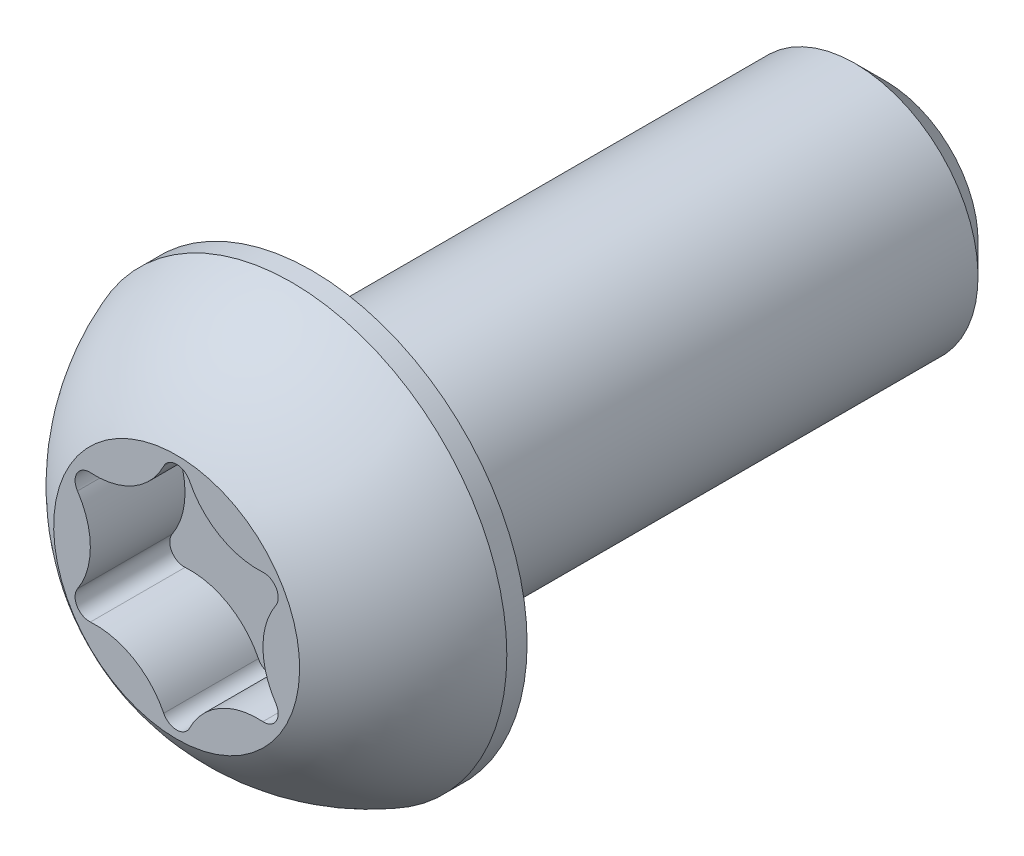
SolidWorks part; units mm, degrees
material "Plain Carbon Steel"
ref_plane "Front" through (0, 0, 0) normal (0, 0, 1) x (1, 0, 0)
ref_plane "Top" through (0, 0, 0) normal (0, 1, 0) x (1, 0, 0)
ref_plane "Right" through (0, 0, 0) normal (1, 0, 0) x (0, 0, -1)
sketch "Sketch1" plane through (0, 0, 0) normal (1, 0, 0) x (0, 0, -1)
  line L2 (-7, 3) -> (7, 3)
  line L3 (7, 3) -> (7, 0)
  line L4 (7, 0) -> (-7, 0)
  line L6 (-7.495, 5.25) -> (-7, 5.25) construction
  line L7 (7, 3) -> (7, -3) construction
  line L8 (-10.3, 0) -> (-7, 0) construction
  line L9 (-7, 5.25) -> (-7, -5.25) construction
  line L11 (-7, 3) -> (-7, 0)
  line L14 (-10.3, 0) -> (-10.3, 3) construction
  line L15 (7, -3) -> (6, -3) construction
  arc A3 (-10.3, 3) -> (-7.495, 5.25) centre (-5.5887, 0) cw construction
  point P10 (5.5, -3)
  point P15 (0, 0)
  dimension "Thread OD" = 6
  dimension "D1" = 0.495
  dimension "Head Height" = 3.3
  dimension "Head Diameter" = 10.5
  dimension "Length" = 14
  dimension "Thread Pitch" = 1
  dimension "D2" = 1.5
sketch "Sketch2" plane through (0, 0, 0) normal (0, 0, 1) x (1, 0, 0)
  line L0 (0, 0) -> (-2.4307, 1.4034)
  line L1 (0, 0) -> (-2.4307, -1.4034)
  line L2 (0, 2.8067) -> (0, 2.4559) construction
  line L3 (0, 2.4559) -> (0, 2.105) construction
  circle A0 centre (0, 0) radius 2.8067 construction
  circle A1 centre (0, 0) radius 2.105 construction
  circle A2 centre (0, 0) radius 2.4559 construction
  arc A4 (-2.4185, 1.0329) -> (-2.4185, -1.0329) centre (-3.9636, 0) cw
  arc A5 (-2.4185, 1.0329) -> (-2.4307, 1.4034) centre (-2.1268, 1.2279) cw
  arc A6 (-2.4185, -1.0329) -> (-2.4307, -1.4034) centre (-2.1268, -1.2279) ccw
  point P3 (0, -2.8067)
  dimension "Torx OD" = 5.6134
  dimension "D1" = 4.2101
  dimension "D2" = 60
sketch "Sketch12" plane through (0, 0, 0) normal (1, 0, 0) x (0, 0, -1)
  line L0 (-7, 3) -> (-7, 0) construction
  line L1 (7, 0) -> (-7, 0) construction
  line L2 (7, 3) -> (7, 0) construction
  line L3 (-7, 3) -> (7, 3) construction
  line L4 (-7, 3) -> (-7, 0)
  line L5 (7, 0) -> (-7, 0)
  line L6 (7, 3) -> (7, 0)
  line L7 (-7, 3) -> (7, 3)
revolve "Revolve1" add sketch "Sketch12" angle 360 about L5
sketch "Sketch7" plane through (0, 0, 0) normal (1, 0, 0) x (0, 0, -1)
  line L0 (-10.3, 0) -> (-10.3, 3) construction
  line L6 (-7.495, 5.25) -> (-7, 5.25) construction
  line L8 (-10.3, 0) -> (-7, 0) construction
  line L11 (-7, 5.25) -> (-7, -5.25) construction
  line L12 (-7.495, 5.25) -> (-7, 5.25)
  line L13 (-10.3, 0) -> (-7, 0)
  line L15 (-7, 5.25) -> (-7, 0)
  line L16 (-10.3, 3) -> (-10.3, 0)
  arc A2 (-7.495, 5.25) -> (-10.3, 3) centre (-5.5887, 0) ccw construction
  arc A3 (-7.495, 5.25) -> (-10.3, 3) centre (-5.5887, 0) ccw
revolve "Revolve2" add sketch "Sketch7" angle 360 mid plane about L13
sketch "Sketch11" plane through (0, 0, 10.3) normal (0, 0, 1) x (1, 0, 0)
  line L0 (0, 0) -> (-2.4307, 1.4034) construction
  line L1 (0, 0) -> (-2.4307, -1.4034) construction
  line L2 (0, 0) -> (-2.4307, 1.4034)
  line L3 (0, 0) -> (-2.4307, -1.4034)
  arc A0 (-2.4307, 1.4034) -> (-2.4185, 1.0329) centre (-2.1268, 1.2279) ccw construction
  arc A1 (-2.4185, -1.0329) -> (-2.4185, 1.0329) centre (-3.9636, 0) ccw construction
  arc A3 (-2.4185, -1.0329) -> (-2.4307, -1.4034) centre (-2.1268, -1.2279) ccw construction
  arc A4 (-2.4307, 1.4034) -> (-2.4185, 1.0329) centre (-2.1268, 1.2279) ccw
  arc A5 (-2.4185, -1.0329) -> (-2.4185, 1.0329) centre (-3.9636, 0) ccw
  arc A7 (-2.4185, -1.0329) -> (-2.4307, -1.4034) centre (-2.1268, -1.2279) ccw
extrude "Cut-Extrude4" cut sketch "Sketch11" against normal blind 2.31
pattern_circular "CirPattern1" count 6 over 360 of "Cut-Extrude4"
chamfer "Chamfer1" distance 0.75 angle 45 1 edges at (0, 3, -7)
split "Split1" [suppressed] bodies to split 122 113
sketch "Sketch13" [suppressed] plane through (0, 0, -7) normal (0, 0, -1) x (-1, 0, 0)
  circle A0 centre (0, 0) radius 3 construction
  circle A1 centre (0, 0) radius 3
curve "Helix/Spiral1" [suppressed] pitch 1 height 15 turns 15
sketch "Sketch14" [suppressed] plane through (0, 0, 0) normal (1, 0, 0) x (0, 0, -1)
  line L0 (7.9375, 3.1083) -> (6.9375, 3.1083) construction
  line L1 (6.9375, 3.1083) -> (7.4375, 2.2422) construction
  line L2 (7.4375, 2.2422) -> (7.9375, 3.1083) construction
  line L3 (7.875, 3) -> (7, 3) construction
  line L4 (7.4375, 3.1083) -> (7.4375, 3) construction
  line L5 (7.9062, 3.0541) -> (6.9687, 3.0541) construction
  line L6 (7.5, 2.3505) -> (7.375, 2.3505) construction
  line L7 (7.4375, 2.3505) -> (7.4375, 2.2422) construction
  line L8 (7.375, 2.3505) -> (6.9687, 3.0541)
  line L9 (6.9687, 3.0541) -> (7.9062, 3.0541)
  line L10 (7.9062, 3.0541) -> (7.5, 2.3505)
  line L11 (7.5, 2.3505) -> (7.375, 2.3505)
  point P11 (7.4375, 3.0541)
  dimension "D1" = 1
  dimension "D2" = 0.125
sweep "Cut-Sweep1" [suppressed] cut profiles "Sketch14" path "Helix/Spiral1"
combine bodies "Combine1" [suppressed] operation type add bodies to combine 125 127
equation "\"D3@Helix/Spiral1\" = \"Length@Sketch1\" + \"Thread Pitch@Sketch1\""
equation "\"D1@Chamfer1\"=\"D4@Helix/Spiral1\" * .75"
equation "\"D1@Sketch1\" = \"Head Height@Sketch1\" * .15"
equation "\"D1@Cut-Extrude4\" = \"Head Height@Sketch1\" * .7"
equation "\"D2@Sketch1\"=\"Thread Pitch@Sketch1\"*1.5"
equation "\"D1@Sketch14\"=\"Thread Pitch@Sketch1\""
equation "\"D2@Sketch14\"=\"D1@Sketch14\"/ 1/8"
equation "\"D4@Helix/Spiral1\"=\"Thread Pitch@Sketch1\""
equation "\"D1@Sketch2\"=\"Torx OD@Sketch2\"*.75"
